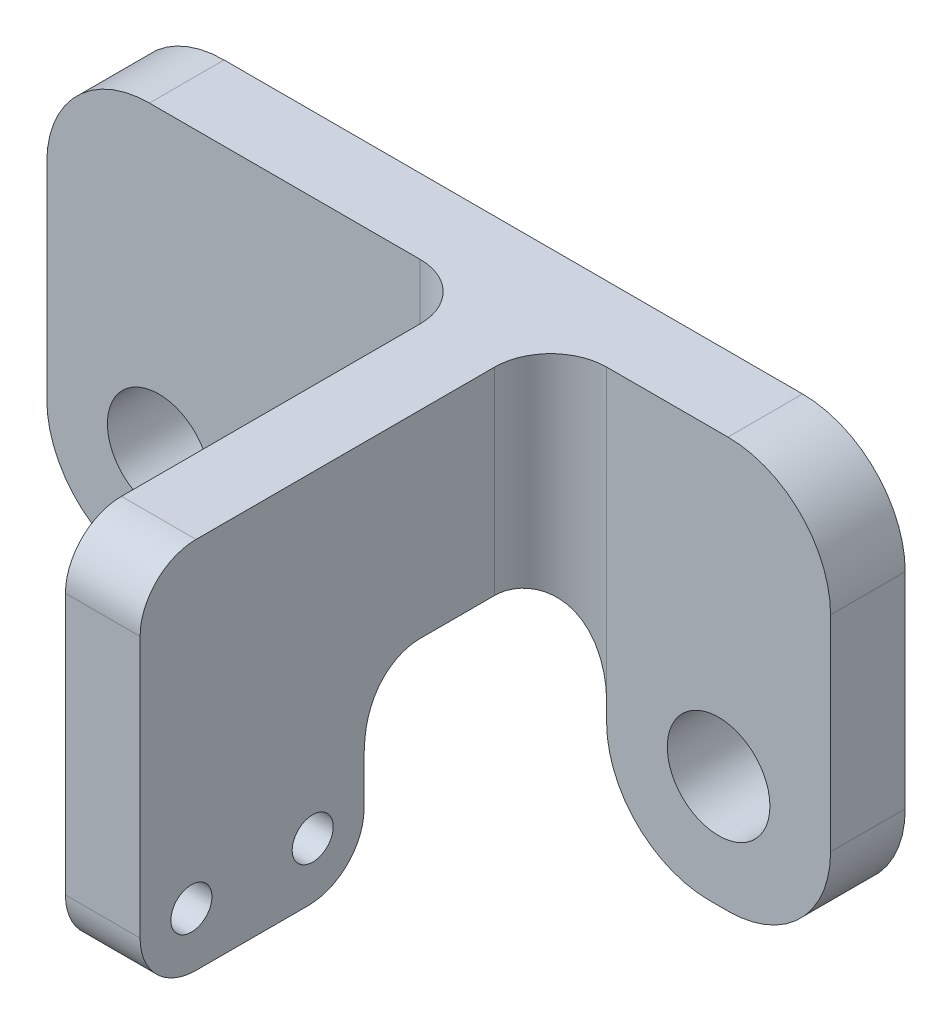
SolidWorks part; units mm, degrees
ref_plane "Front Plane" through (0, 0, 0) normal (0, 0, 1) x (1, 0, 0)
ref_plane "Top Plane" through (0, 0, 0) normal (0, 1, 0) x (1, 0, 0)
ref_plane "Right Plane" through (0, 0, 0) normal (1, 0, 0) x (0, 0, -1)
sketch "Sketch1" plane through (0, 0, 0) normal (0, 0, 1) x (1, 0, 0)
  line L0 (0, 0) -> (15, 0)
  line L1 (0, 0) -> (0, 22.3608) construction
  line L2 (-9, 6) -> (-21, 6)
  line L3 (9, -6) -> (21, -6)
  line L4 (9, -6) -> (9, 6)
  line L5 (9, 6) -> (21, 6)
  line L6 (21, -6) -> (21, 6)
  line L7 (9, -6) -> (21, 6) construction
  line L8 (9, 6) -> (21, -6) construction
  line L9 (21, 6) -> (-21, 6)
  line L10 (21, 6) -> (21, 16)
  line L11 (21, 16) -> (-21, 16)
  line L12 (0, 6) -> (0, 16)
  line L13 (-21, -6) -> (-21, 6)
  line L14 (-9, -6) -> (-21, -6)
  line L15 (-9, -6) -> (-9, 6)
  line L16 (-21, 6) -> (-21, 16)
  circle A0 centre (15, 0) radius 2.75
  circle A1 centre (-15, 0) radius 2.75
  dimension "D2" = 5.5
  dimension "D1" = 15
  dimension "D3" = 12
  dimension "D4" = 12
  dimension "D5" = 10
extrude "Boss-Extrude1" add sketch "Sketch1" along normal blind 4 contours L16 L2 L9 L12 L11 | L14 L15 L2 L13 A1 | L12 L9 L5 L10 L11 | A0 L4 L3 L6 L5 region at (9.1697, 3, 0) region at (10.5, 11, 0) region at (-10.5, 11, 0) region at (-9.1697, 0, 0)
sketch "Sketch2" plane through (0, 0, 4) normal (0, 0, 1) x (1, 0, 0)
  line L6 (0, 0) -> (0, 18.6679) construction
  line L7 (9, 6) -> (-9, 6) construction
  line L8 (2, 6) -> (6, 6)
  line L9 (2, 6) -> (2, 16)
  line L10 (2, 16) -> (6, 16)
  line L11 (6, 6) -> (6, 16)
  line L12 (21, 16) -> (-21, 16) construction
  dimension "D1" = 4
  dimension "D2" = 2
extrude "Boss-Extrude2" add sketch "Sketch2" along normal blind 22
sketch "Sketch3" plane through (0, 6, 0) normal (0, -1, 0) x (1, 0, 0)
  line L0 (6, 26) -> (6, 4) construction
  line L1 (2, 26) -> (6, 26)
  line L2 (2, 26) -> (2, 14)
  line L3 (2, 14) -> (6, 14)
  line L4 (6, 26) -> (6, 14)
  dimension "D1" = 12
extrude "Boss-Extrude3" add sketch "Sketch3" along normal blind 10
sketch "Sketch4" plane through (2, 0, 0) normal (-1, 0, 0) x (0, 0, 1)
  line L0 (20, -4) -> (20, 16.9921) construction
  line L1 (26, -4) -> (14, -4) construction
  line L2 (20, -1) -> (16.75, -1)
  circle A0 centre (16.75, -1) radius 1.1
  circle A1 centre (23.25, -1) radius 1.1
  dimension "D2" = 2.2
  dimension "D1" = 3.25
  dimension "D3" = 3
extrude "Cut-Extrude1" cut sketch "Sketch4" against normal blind 18 contours A1 | A0 region at (2, -1, 23.25)
fillet "Fillet1" radius 5.5 8 edges at (-21, 16, 2) (21, 16, 2) (21, -6, 2) (9, -6, 2) (9, 6, 2) (-9, 6, 2) (-9, -6, 2) (-21, -6, 2)
fillet "Fillet2" radius 3 7 edges at (2.75, 6, 14) (4.7856, 5.8476, 14) (6, 10.6995, 4) (2, 11, 4) (4, 16, 26) (4, -4, 26) (4, -4, 14)
